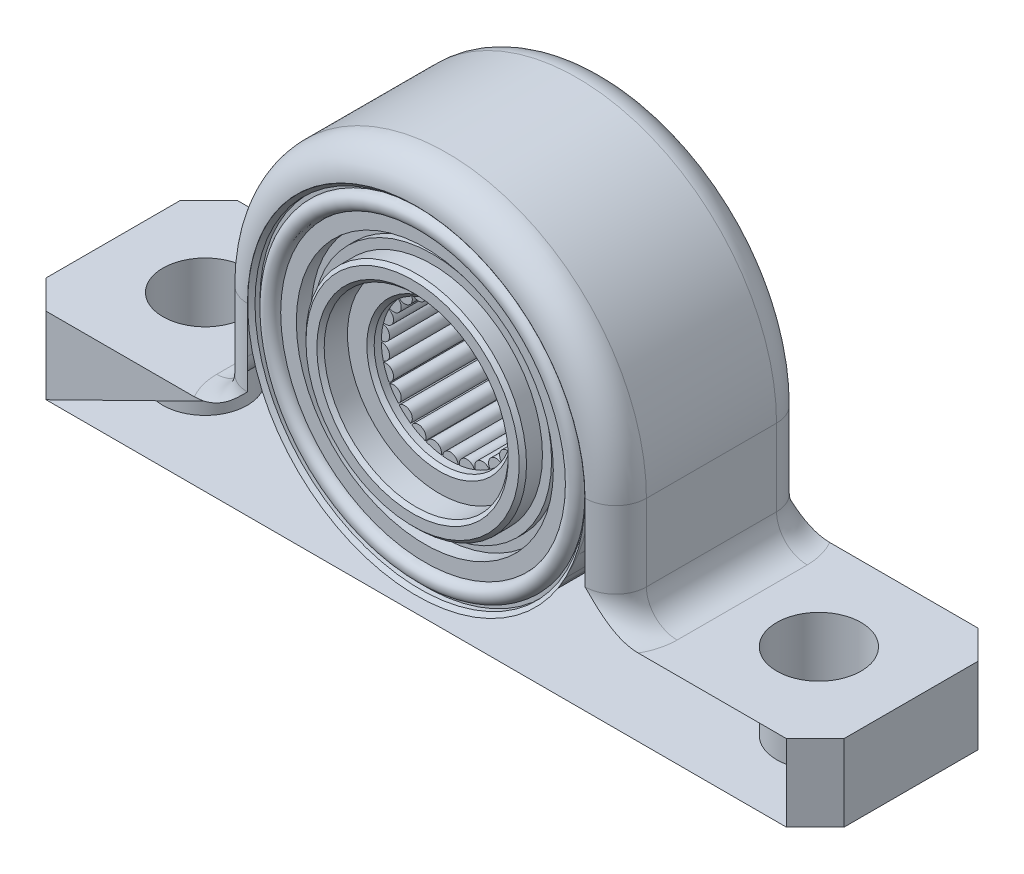
SolidWorks part; units mm, degrees
ref_plane "Front Plane" through (0, 0, 0) normal (0, 0, 1) x (1, 0, 0)
ref_plane "Top Plane" through (0, 0, 0) normal (0, 1, 0) x (1, 0, 0)
ref_plane "Right Plane" through (0, 0, 0) normal (1, 0, 0) x (0, 0, -1)
sketch "Sketch1" plane through (0, 0, 0) normal (0, 0, 1) x (1, 0, 0)
  line L0 (0, 19.8438) -> (0, -19.8438) construction
  line L1 (-41.275, -19.8438) -> (41.275, -19.8437) construction
  line L2 (-31.75, -19.8438) -> (31.75, -19.8437) construction
  line L3 (-41.275, -19.8438) -> (-41.275, -11.9062)
  line L4 (-41.275, -11.9062) -> (-20.6375, -11.9062)
  line L5 (-20.6375, -0.7938) -> (-20.6375, -11.9062)
  line L6 (-23.8125, -19.8438) -> (-23.8125, -11.9062) construction
  circle A0 centre (-31.75, -19.8438) radius 4.3656
  circle A1 centre (31.75, -19.8437) radius 4.3656
  circle A2 centre (0, -0.7937) radius 6.35
  circle A3 centre (0, -0.7937) radius 20.6375
  circle A4 centre (-31.75, -19.8438) radius 7.9375
  circle A5 centre (0, -0.7937) radius 17.0656
  circle A6 centre (0, -0.7937) radius 9.525
  circle A7 centre (0, -0.7937) radius 7.1438 construction
  point P5 (0, -11.9062)
  point P6 (0, -0.7937)
  point P7 (-31.75, -19.8438)
  point P8 (31.75, -19.8437)
  point P22 (0, 5.5563)
  point P23 (0, 16.2719)
  point P25 (0, 14.1174)
  point P26 (0, 12.5016)
  point P27 (0, 10.6164)
  point P28 (0, 8.7313)
  dimension "D1" = 3.175
  dimension "Mounting Hole" = 8.7312
  dimension "ID" = 12.7
  dimension "D3" = 10.7156
  dimension "D4" = 19.05
  dimension "D9" = 14.2875
  dimension "Height" = 39.6875
  dimension "Length" = 82.55
  dimension "Lit G" = 7.9375
  dimension "Center Height" = 19.05
  dimension "Mounting Center" = 63.5
  dimension "D2" = 14.2875
  dimension "D5" = 7.5406
  dimension "D6" = 2.1545
  dimension "D7" = 1.8852
  dimension "D8" = 1.8852
sketch "Sketch3" plane through (0, 0, 0) normal (0, 1, 0) x (1, 0, 0)
  line L0 (0, 9.906) -> (0, -9.906) construction
  dimension "Width" = 19.812
sketch "Sketch6" plane through (0, 0, 0) normal (1, 0, 0) x (0, 0, -1)
  line L0 (-9.0193, 15.8909) -> (-9.0193, 16.2719)
  line L1 (-9.906, 16.2719) -> (9.906, 16.2719) construction
  line L2 (-9.906, 16.2719) -> (-9.906, -0.7937) construction
  line L3 (-9.906, -0.7937) -> (9.906, -0.7937) construction
  line L4 (9.906, 16.2719) -> (9.906, -0.7937) construction
  line L5 (-9.0193, 14.1174) -> (-9.0193, 12.5016)
  line L6 (-7.4953, 12.5016) -> (-9.0193, 12.5016)
  line L7 (-8.2573, 11.559) -> (-8.2573, 10.6164)
  line L8 (-8.2573, 10.6164) -> (-10.287, 10.6164)
  line L9 (-10.287, 10.6164) -> (-10.287, 8.7313)
  line L10 (-8.2573, 11.559) -> (-7.4953, 11.559)
  line L11 (-7.4953, 11.559) -> (-7.4953, 12.5016)
  line L12 (-10.287, 8.7313) -> (-7.4953, 8.7313)
  line L13 (-7.4953, 8.7313) -> (-7.4953, 5.5563)
  line L14 (-7.4953, 5.5563) -> (7.4953, 5.5563)
  line L15 (-9.0193, 16.2719) -> (9.0193, 16.2719)
  line L16 (0, -0.7937) -> (0, 32.5437) construction
  line L17 (0, 19.8438) -> (0, -19.8438) construction
  line L18 (0, 19.8438) -> (0, -21.4312) construction
  line L19 (7.4953, 8.7313) -> (7.4953, 5.5563)
  line L20 (10.287, 8.7313) -> (7.4953, 8.7313)
  line L21 (7.4953, 11.559) -> (7.4953, 12.5016)
  line L22 (8.2573, 11.559) -> (7.4953, 11.559)
  line L23 (10.287, 10.6164) -> (10.287, 8.7313)
  line L24 (8.2573, 10.6164) -> (10.287, 10.6164)
  line L25 (8.2573, 11.559) -> (8.2573, 10.6164)
  line L26 (7.4953, 12.5016) -> (9.0193, 12.5016)
  line L27 (9.0193, 14.1174) -> (9.0193, 12.5016)
  line L28 (9.0193, 15.8909) -> (9.0193, 16.2719)
  arc A0 (-9.0193, 15.8909) -> (-9.0193, 14.1174) centre (-9.0193, 15.0041) ccw
  arc A1 (9.0193, 15.8909) -> (9.0193, 14.1174) centre (9.0193, 15.0041) cw
  point P40 (0, 16.2719)
  point P41 (0, 5.5563)
  dimension "D1" = 0.381
  dimension "D2" = 0.381
  dimension "D3" = 1.524
  dimension "D4" = 0.762
  dimension "D5" = 0.762
  dimension "D6" = 14.9905
revolve "Revolve1" add sketch "Sketch6" angle 360 about L3
sketch "Sketch7" plane through (0, 0, 0) normal (0, 0, 1) x (1, 0, 0)
  line L0 (0, 19.8438) -> (0, -19.8438) construction
  line L1 (-0.7937, 6.35) -> (0, -0.7937) construction
  line L2 (0, -0.7937) -> (0.7937, 6.35) construction
  circle A0 centre (0, 6.35) radius 0.7938
  circle A1 centre (0, -0.7937) radius 7.1438 construction
  circle A2 centre (0, -0.7937) radius 6.35 construction
  dimension "D1" = 1.5875
  dimension "D2" = 12.68
sketch "Sketch8" plane through (0, 0, 7.4953) normal (0, 0, 1) x (1, 0, 0)
  circle A0 centre (0, -0.7937) radius 7.1438 construction
  circle A1 centre (0, -0.7937) radius 7.1438
extrude "Cut-Extrude2" cut sketch "Sketch8" against normal through all
sketch "Sketch9" plane through (0, 0, 0) normal (0, 0, 1) x (1, 0, 0)
  circle A0 centre (0, 6.35) radius 0.7938 construction
  circle A1 centre (0, 6.35) radius 0.7938
extrude "Boss-Extrude2" add sketch "Sketch9" along normal mid plane 12.742
pattern_circular "CirPattern1" count 26 over 360 of "Boss-Extrude2"
chamfer "Chamfer2" distance 0.381 angle 45 6 edges at (9.525, -0.7937, -10.287) (11.4102, -0.7937, -10.287) (11.4102, -0.7937, 10.287) (9.525, -0.7937, 10.287) (7.1438, -0.7937, -7.4953) (7.1438, -0.7937, 7.4953)
sketch "Sketch4" plane through (0, 0, 0) normal (0, 0, 1) x (1, 0, 0)
  line L0 (-41.275, -19.8438) -> (-41.275, -11.9062) construction
  line L1 (-41.275, -11.9062) -> (-20.6375, -11.9062) construction
  line L2 (-41.275, -19.8438) -> (41.275, -19.8437) construction
  line L3 (-41.275, -19.8438) -> (-41.275, -11.9062)
  line L4 (-41.275, -11.9062) -> (-20.6375, -11.9062)
  line L5 (-41.275, -19.8438) -> (41.275, -19.8437)
  line L6 (-20.6375, -0.7938) -> (-20.6375, -11.9062) construction
  line L7 (-20.6375, -0.7938) -> (-20.6375, -11.9062)
  line L8 (0, 19.8438) -> (0, -19.8438) construction
  line L9 (20.6375, -0.7937) -> (20.6375, -11.9062)
  line L10 (41.275, -11.9062) -> (20.6375, -11.9062)
  line L11 (41.275, -19.8437) -> (41.275, -11.9062)
  circle A0 centre (0, -0.7937) radius 20.6375 construction
  arc A1 (20.6375, -0.7937) -> (-20.6375, -0.7938) centre (0, -0.7937) ccw
  circle A2 centre (0, -0.7937) radius 17.0656 construction
  circle A3 centre (0, -0.7937) radius 17.0656
extrude "Boss-Extrude1" add sketch "Sketch4" along normal up to vertex (9.906 mm away) and the other way up to vertex (9.906 mm away) up to point (0, 0, 9.906) other way up to point (0, 0, -9.906)
sketch "Sketch5" plane through (0, -11.9062, 0) normal (0, 1, 0) x (1, 0, 0)
  circle A0 centre (-31.75, 0) radius 4.3656
  circle A1 centre (31.75, 0) radius 4.3656
  dimension "D1" = 8.7312
extrude "Cut-Extrude1" cut sketch "Sketch5" against normal through all
chamfer "Chamfer1" distance 2.9718 angle 45 4 edges at (41.275, -15.875, -9.906) (41.275, -15.875, 9.906) (-41.275, -15.875, 9.906) (-41.275, -15.875, -9.906)
fillet "Fillet1" radius 3.175 6 edges at (20.6375, -6.35, -9.906) (0, 19.8438, -9.906) (20.6375, -6.35, 9.906) (0, 19.8438, 9.906) (-20.6375, -6.35, -9.906) (-20.6375, -6.35, 9.906)
fillet "Fillet3" radius 3.175 6 edges at (-19.7076, -11.9062, -8.9761) (-19.7076, -11.9062, 8.9761) (-20.6375, -11.9062, 0) (19.7076, -11.9062, -8.9761) (20.6375, -11.9062, 0) (19.7076, -11.9062, 8.9761) tangent propagation no
chamfer "Chamfer3" distance 0.381 angle 45 2 edges at (17.0656, -0.7937, -9.906) (17.0656, -0.7937, 9.906)
equation "\"D1@Sketch5\"=\"Mounting Hole@Sketch1\""
equation "\"D1@Chamfer1\"=\"Width@Sketch3\"*.15"
equation "\"D1@Fillet1\"=\"D1@Sketch1\""
equation "\"D1@Fillet3\"=\"D1@Fillet1\""
equation "\"D3@Sketch1\"=\"D2@Sketch1\"*.750"
equation "\"D4@Sketch1\"=\"ID@Sketch1\"*1.5"
equation "\"D6@Sketch1\"=\"D5@Sketch1\"/3.5"
equation "\"D7@Sketch1\"=\"D5@Sketch1\"/4"
equation "\"D8@Sketch1\"=\"D5@Sketch1\"/4"
equation "\"D9@Sketch1\"=\"ID@Sketch1\"*1.125"
equation "\"D1@CirPattern1\"=(360/\"D2@Sketch7\")-2"
equation "\"D1@Boss-Extrude2\"=\"D6@Sketch6\"*.85"
